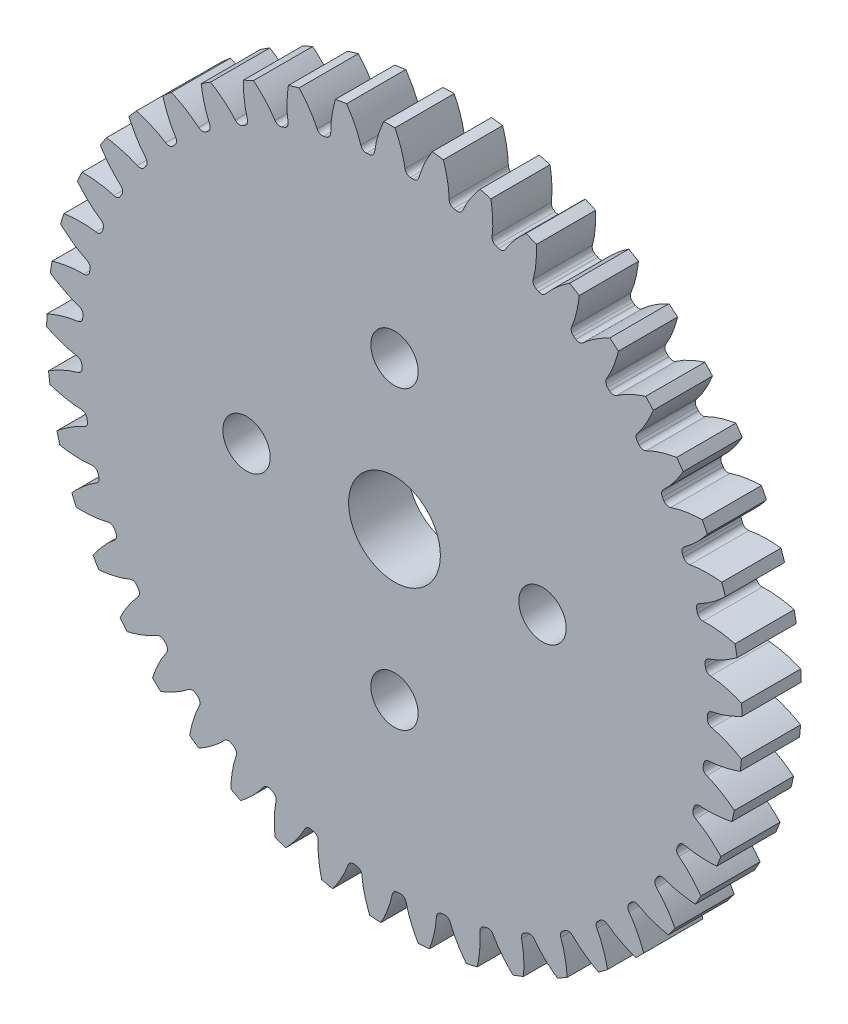
SolidWorks part; units mm, degrees
material "AISI 304"
ref_plane "前基準面" through (0, 0, 0) normal (0, 0, 1) x (1, 0, 0)
ref_plane "上基準面" through (0, 0, 0) normal (0, 1, 0) x (1, 0, 0)
ref_plane "右基準面" through (0, 0, 0) normal (1, 0, 0) x (0, 0, -1)
sketch "草圖1" plane through (0, 0, 0) normal (0, 0, 1) x (1, 0, 0)
  spline S0 degree 4 poles (21.1431, 0) (21.1527, 0.0002) (21.1798, 0.0011) (21.2308, 0.0049) (21.3139, 0.0137) (21.4195, 0.0291) (21.5555, 0.0537) (21.7148, 0.0886) (21.8889, 0.1333) (22.0772, 0.1885) (22.2637, 0.2495) (22.4486, 0.3158) (22.6316, 0.3867) (22.8516, 0.4784) (23.1133, 0.5963) (23.4155, 0.7455) (23.7538, 0.9282) (24.0934, 1.1285) (24.4231, 1.3372) (24.7506, 1.5611) (25.0635, 1.787) (25.3824, 2.0346) (25.6736, 2.2699) (25.9925, 2.5476) (26.2478, 2.7759) (26.5763, 3.0917) (26.7679, 3.2826) (26.989, 3.511) (27.0857, 3.615) (27.1453, 3.679) knots 0 0 0 0 0 0.005377 0.015084 0.028532 0.04661 0.064855 0.092111 0.119476 0.146842 0.174209 0.201575 0.228941 0.256307 0.307035 0.361767 0.4165 0.471232 0.525964 0.580697 0.635429 0.690161 0.744894 0.799626 0.854358 0.909091 0.954545 1 1 1 1 1 construction
  spline S1 degree 4 poles (21.1431, 0) (21.1527, 0.0002) (21.1798, 0.0011) (21.2308, 0.0049) (21.3139, 0.0137) (21.4195, 0.0291) (21.5555, 0.0537) (21.7148, 0.0886) (21.8889, 0.1333) (22.0772, 0.1885) (22.2637, 0.2495) (22.4486, 0.3158) (22.6316, 0.3867) (22.8516, 0.4784) (23.1133, 0.5963) (23.4155, 0.7455) (23.7538, 0.9282) (24.0934, 1.1285) (24.4231, 1.3372) (24.7506, 1.5611) (25.0635, 1.787) (25.3824, 2.0346) (25.6736, 2.2699) (25.9925, 2.5476) (26.2478, 2.7759) (26.5051, 3.0232) (26.6294, 3.1453) (26.6924, 3.2084) knots 0 0 0 0 0 0.005377 0.015084 0.028532 0.04661 0.064855 0.092111 0.119476 0.146842 0.174209 0.201575 0.228941 0.256307 0.307035 0.361767 0.4165 0.471232 0.525964 0.580697 0.635429 0.690161 0.744894 0.799626 0.854358 0.909091 0.909091 0.909091 0.909091 0.909091
sketch "草圖2" plane through (0, 0, 0) normal (0, 0, 1) x (1, 0, 0)
  line L0 (0, 0) -> (28.067, 0) construction
  line L1 (0, 0) -> (22.4954, -0.4546) construction
  arc A4 (22.4954, -0.4546) -> (22.4975, 0.3353) centre (0, 0) ccw
  circle A5 centre (0, 0) radius 23.5
  circle A6 centre (0, 0) radius 21.145
  circle A7 centre (0, 0) radius 21.25
  spline S0 degree 4 poles (-5.5638, 1999.6537) (18.2117, 27.4514) (19.2412, 0.4392) (20.293, -0.0955) (21.3139, 0.0137) (21.4195, 0.0291) (21.5555, 0.0537) (21.7148, 0.0886) (21.8889, 0.1333) (22.0772, 0.1885) (22.2637, 0.2495) (22.4486, 0.3158) (22.6316, 0.3867) (22.8516, 0.4784) (23.1133, 0.5963) (23.4155, 0.7455) (23.7538, 0.9282) (24.0934, 1.1285) (24.4231, 1.3372) (24.7506, 1.5611) (25.0635, 1.787) (25.3824, 2.0346) (25.6736, 2.2699) (25.9925, 2.5476) (27.2244, 3.6491) (30.8424, 7.5274) (-13.0904, -35.9082) (1440.1843, 1418.0706) knots -0.525893 -0.525893 -0.525893 -0.525893 -0.525893 0.005377 0.015084 0.028532 0.04661 0.064855 0.092111 0.119476 0.146842 0.174209 0.201575 0.228941 0.256307 0.307035 0.361767 0.4165 0.471232 0.525964 0.580697 0.635429 0.690161 0.744894 0.799626 0.854358 1.746617 1.746617 1.746617 1.746617 1.746617 only from (21.1431, 0) to (26.6924, 3.2084) construction
  spline S1 degree 4 poles (21.1431, 0) (21.1527, 0.0002) (21.1798, 0.0011) (21.2308, 0.0049) (21.3139, 0.0137) (21.4195, 0.0291) (21.5555, 0.0537) (21.7148, 0.0886) (21.8889, 0.1333) (22.0772, 0.1885) (22.2637, 0.2495) (22.4486, 0.3158) (22.6316, 0.3867) (22.8516, 0.4784) (23.1133, 0.5963) (23.4155, 0.7455) (23.7538, 0.9282) (24.0934, 1.1285) (24.4231, 1.3372) (24.7506, 1.5611) (25.0635, 1.787) (25.3824, 2.0346) (25.6736, 2.2699) (25.9925, 2.5476) (26.2478, 2.7759) (26.5051, 3.0232) (26.6294, 3.1453) (26.6924, 3.2084) knots 0 0 0 0 0 0.005377 0.015084 0.028532 0.04661 0.064855 0.092111 0.119476 0.146842 0.174209 0.201575 0.228941 0.256307 0.307035 0.361767 0.4165 0.471232 0.525964 0.580697 0.635429 0.690161 0.744894 0.799626 0.854358 0.909091 0.909091 0.909091 0.909091 0.909091
  spline S2 degree 4 poles (21.1258, -0.8542) (21.1354, -0.8548) (21.1624, -0.8568) (21.2133, -0.8626) (21.296, -0.8749) (21.4008, -0.8945) (21.5357, -0.9246) (21.6935, -0.9659) (21.8657, -1.0175) (22.0515, -1.0803) (22.2355, -1.1488) (22.4175, -1.2225) (22.5975, -1.3008) (22.8136, -1.4013) (23.0703, -1.5296) (23.3663, -1.6909) (23.6969, -1.8871) (24.0281, -2.101) (24.3491, -2.3229) (24.6673, -2.5598) (24.9709, -2.7981) (25.2795, -3.0585) (25.5609, -3.3053) (25.8684, -3.5957) (26.1142, -3.8341) (26.3613, -4.0916) (26.4805, -4.2186) (26.541, -4.2842) knots 0 0 0 0 0 0.005377 0.015084 0.028532 0.04661 0.064855 0.092111 0.119476 0.146842 0.174209 0.201575 0.228941 0.256307 0.307035 0.361767 0.4165 0.471232 0.525964 0.580697 0.635429 0.690161 0.744894 0.799626 0.854358 0.909091 0.909091 0.909091 0.909091 0.909091
  dimension "D1" = 45
  dimension "D2" = 47
  dimension "D3" = 42.5
  dimension "D4" = 42.29
  dimension "D5" = 0.79
extrude "填料-伸長1" add sketch "草圖2" along normal blind 4 contours A5
sketch "草圖3" plane through (0, 0, 4) normal (0, 0, 1) x (1, 0, 0)
  circle A0 centre (0, 0) radius 23.5 construction
  circle A1 centre (0, 0) radius 21.145 construction
  arc A2 (23.4359, -1.7343) -> (23.4869, 0.786) centre (0, 0) ccw
  arc A3 (21.1277, -0.8543) -> (21.145, 0) centre (0, 0) ccw
  spline S0 degree 4 poles (-86.3501, -1997.7962) (17.0878, -28.1648) (19.2078, -1.2162) (20.2803, -0.7245) (21.296, -0.8749) (21.4008, -0.8945) (21.5357, -0.9246) (21.6935, -0.9659) (21.8657, -1.0175) (22.0515, -1.0803) (22.2355, -1.1488) (22.4175, -1.2225) (22.5975, -1.3008) (22.8136, -1.4013) (23.0703, -1.5296) (23.3663, -1.6909) (23.6969, -1.8871) (24.0281, -2.101) (24.3491, -2.3229) (24.6673, -2.5598) (24.9709, -2.7981) (25.2795, -3.0585) (25.5609, -3.3053) (25.8684, -3.5957) (27.0547, -4.7461) (30.5131, -8.7674) (-11.629, 36.4077) (1381.7149, -1475.0996) knots -0.525893 -0.525893 -0.525893 -0.525893 -0.525893 0.005377 0.015084 0.028532 0.04661 0.064855 0.092111 0.119476 0.146842 0.174209 0.201575 0.228941 0.256307 0.307035 0.361767 0.4165 0.471232 0.525964 0.580697 0.635429 0.690161 0.744894 0.799626 0.854358 1.746617 1.746617 1.746617 1.746617 1.746617 only from (21.1258, -0.8542) to (26.541, -4.2842) construction
  spline S1 degree 4 poles (-5.5638, 1999.6537) (18.2117, 27.4514) (19.2412, 0.4392) (20.293, -0.0955) (21.3139, 0.0137) (21.4195, 0.0291) (21.5555, 0.0537) (21.7148, 0.0886) (21.8889, 0.1333) (22.0772, 0.1885) (22.2637, 0.2495) (22.4486, 0.3158) (22.6316, 0.3867) (22.8516, 0.4784) (23.1133, 0.5963) (23.4155, 0.7455) (23.7538, 0.9282) (24.0934, 1.1285) (24.4231, 1.3372) (24.7506, 1.5611) (25.0635, 1.787) (25.3824, 2.0346) (25.6736, 2.2699) (25.9925, 2.5476) (27.2244, 3.6491) (30.8424, 7.5274) (-13.0904, -35.9082) (1440.1843, 1418.0706) knots -0.525893 -0.525893 -0.525893 -0.525893 -0.525893 0.005377 0.015084 0.028532 0.04661 0.064855 0.092111 0.119476 0.146842 0.174209 0.201575 0.228941 0.256307 0.307035 0.361767 0.4165 0.471232 0.525964 0.580697 0.635429 0.690161 0.744894 0.799626 0.854358 1.746617 1.746617 1.746617 1.746617 1.746617 only from (21.1431, 0) to (26.6924, 3.2084) construction
  spline S2 degree 4 poles (21.1277, -0.8543) (21.1369, -0.8549) (21.1634, -0.8569) (21.2137, -0.8627) (21.296, -0.8749) (21.4008, -0.8945) (21.5357, -0.9246) (21.6935, -0.9659) (21.8657, -1.0175) (22.0515, -1.0803) (22.2355, -1.1488) (22.4175, -1.2225) (22.5975, -1.3008) (22.8136, -1.4013) (23.0465, -1.5177) (23.2329, -1.6183) (23.3741, -1.6985) (23.4359, -1.7343) knots 0.000267 0.000267 0.000267 0.000267 0.000267 0.005377 0.015084 0.028532 0.04661 0.064855 0.092111 0.119476 0.146842 0.174209 0.201575 0.228941 0.256307 0.307035 0.346885 0.346885 0.346885 0.346885 0.346885
  spline S3 degree 4 poles (21.145, 0) (21.1542, 0.0002) (21.1807, 0.0012) (21.2313, 0.0049) (21.3139, 0.0137) (21.4195, 0.0291) (21.5555, 0.0537) (21.7148, 0.0886) (21.8889, 0.1333) (22.0772, 0.1885) (22.2637, 0.2495) (22.4486, 0.3158) (22.6316, 0.3867) (22.8516, 0.4784) (23.089, 0.5853) (23.2793, 0.6784) (23.4237, 0.7527) (23.4869, 0.786) knots 0.000267 0.000267 0.000267 0.000267 0.000267 0.005377 0.015084 0.028532 0.04661 0.064855 0.092111 0.119476 0.146842 0.174209 0.201575 0.228941 0.256307 0.307035 0.346885 0.346885 0.346885 0.346885 0.346885
extrude "除料-伸長1" cut sketch "草圖3" against normal blind 4 contours S3 A2 S2 A3
fillet "圓角1" radius 0.38 2 edges at (21.1277, -0.8543, 2) (21.145, 0, 2)
pattern_circular "環狀複製排列1" count 45 over 360 about axis through (0, 0, 4) along (0, 0, -1) of "圓角1", "除料-伸長1"
sketch "草圖4" plane through (0, 0, 4) normal (0, 0, 1) x (1, 0, 0)
  line L0 (0, 0) -> (10, 0) construction
  circle A0 centre (10, 0) radius 1.6
  dimension "D1" = 3.2
  dimension "D2" = 10
extrude "除料-伸長2" cut sketch "草圖4" against normal blind 4
pattern_circular "環狀複製排列2" count 4 over 360 about axis through (0, 0, 4) along (0, 0, -1) of "除料-伸長2"
sketch "草圖5" plane through (0, 0, 4) normal (0, 0, 1) x (1, 0, 0)
  circle A0 centre (0, 0) radius 22.5 construction
  dimension "D1" = 45
sketch "草圖6" plane through (0, 0, 4) normal (0, 0, 1) x (1, 0, 0)
  circle A0 centre (0, 0) radius 3.1
  dimension "D1" = 6.2
extrude "除料-伸長3" cut sketch "草圖6" against normal through all
equation "\"a\"= 20"
equation "\"M\"= 1"
equation "\"T\"= 45"
equation "\"R\"= 0.38 * \"M\""
equation "\"D\"= \"M\" * \"T\""
equation "\"Da\"= ( \"T\" + 2 ) * \"M\""
equation "\"Df\"= ( \"T\" - 2.5 ) * \"M\""
equation "\"Db\"= \"M\" * \"T\" * cos ( \"a\" )"
equation "\"rb\"= \"Db\" / 2"
equation "\"S\"= pi * \"M\" * 0.5"
